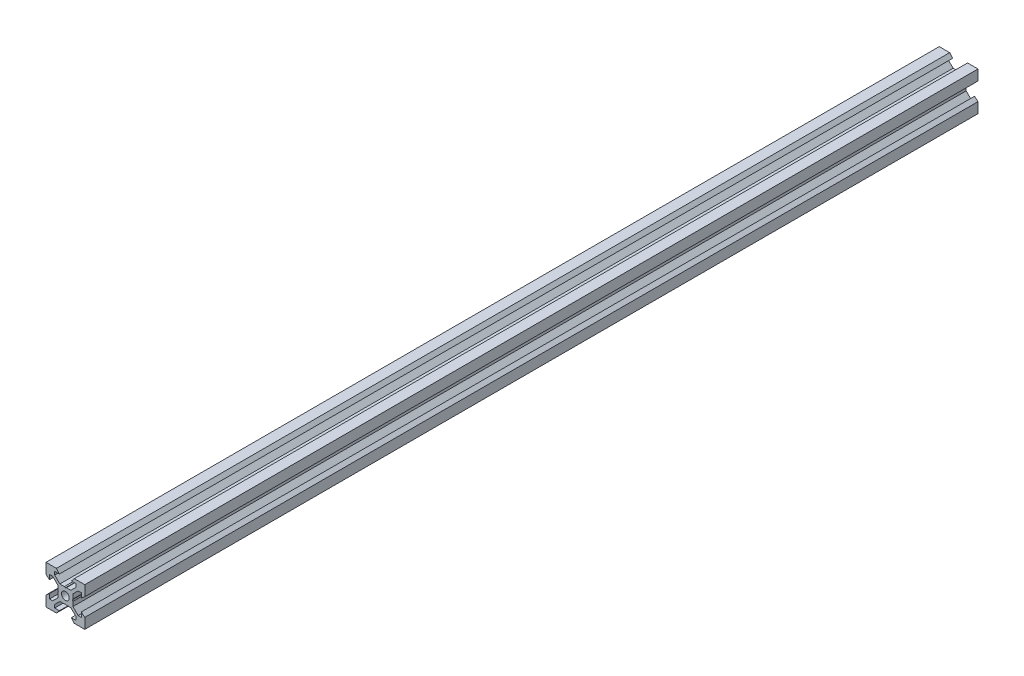
SolidWorks part; units mm, degrees
ref_plane "Front Plane" through (0, 0, 0) normal (0, 0, 1) x (1, 0, 0)
ref_plane "Top Plane" through (0, 0, 0) normal (0, 1, 0) x (1, 0, 0)
ref_plane "Right Plane" through (0, 0, 0) normal (1, 0, 0) x (0, 0, -1)
sketch "Sketch1" plane through (0, 0, 0) normal (0, 0, 1) x (1, 0, 0)
  line L0 (10, 10) -> (4.6104, 10) construction
  line L1 (10, 10) -> (10, 4.6104) construction
  line L2 (10, -10) -> (10, -4.6104) construction
  line L3 (10, -10) -> (4.6104, -10) construction
  line L4 (10, 10) -> (10, 4.6104)
  line L5 (6.5607, 5.5) -> (8.2, 5.5)
  line L6 (5.5, 8.2) -> (5.5, 6.5607)
  line L7 (10, 10) -> (4.6104, 10)
  line L8 (10, 10) -> (10, 4.6104)
  line L9 (6.5607, 5.5) -> (3.9, 2.8393)
  line L10 (5.5, 6.5607) -> (2.8393, 3.9)
  line L11 (10, 4.6104) -> (8.2, 3.1)
  line L12 (4.6104, 10) -> (3.1, 8.2)
  line L13 (8.2, 3.1) -> (8.2, 5.5)
  line L14 (3.1, 8.2) -> (5.5, 8.2)
  line L15 (-6.5607, 5.5) -> (-8.2, 5.5)
  line L16 (6.5607, -5.5) -> (8.2, -5.5)
  line L17 (3.1, -8.2) -> (5.5, -8.2)
  line L18 (8.2, -3.1) -> (8.2, -5.5)
  line L19 (4.6104, -10) -> (3.1, -8.2)
  line L20 (10, -4.6104) -> (8.2, -3.1)
  line L21 (0.5196, -3.9) -> (0, -3.6)
  line L22 (0.5196, 3.9) -> (0, 3.6)
  line L23 (3.6, 0) -> (3.9, -0.5196)
  line L24 (3.9, 0.5196) -> (3.6, 0)
  line L25 (3.9, 0.5196) -> (3.9, 2.8393)
  line L26 (2.8393, 3.9) -> (0.5196, 3.9)
  line L27 (3.9, -2.8393) -> (3.9, -0.5196)
  line L28 (2.8393, -3.9) -> (0.5196, -3.9)
  line L29 (5.5, -6.5607) -> (2.8393, -3.9)
  line L30 (6.5607, -5.5) -> (3.9, -2.8393)
  line L31 (10, -10) -> (10, -4.6104)
  line L32 (10, -10) -> (4.6104, -10)
  line L33 (5.5, -8.2) -> (5.5, -6.5607)
  line L34 (-6.5607, -5.5) -> (-8.2, -5.5)
  line L35 (10, -10) -> (10, -4.6104)
  line L36 (0, 0) -> (0, 8.2) construction
  line L37 (-10, -10) -> (-4.6104, -10) construction
  line L38 (-10, -10) -> (-10, -4.6104) construction
  line L39 (-10, 10) -> (-10, 4.6104) construction
  line L40 (-10, 10) -> (-4.6104, 10) construction
  line L41 (-10, -10) -> (-10, -4.6104)
  line L43 (-5.5, -8.2) -> (-5.5, -6.5607)
  line L44 (-10, -10) -> (-4.6104, -10)
  line L45 (-10, -10) -> (-10, -4.6104)
  line L46 (-6.5607, -5.5) -> (-3.9, -2.8393)
  line L47 (-5.5, -6.5607) -> (-2.8393, -3.9)
  line L48 (-2.8393, -3.9) -> (-0.5196, -3.9)
  line L49 (-3.9, -2.8393) -> (-3.9, -0.5196)
  line L50 (-2.8393, 3.9) -> (-0.5196, 3.9)
  line L51 (-3.9, 0.5196) -> (-3.9, 2.8393)
  line L52 (-3.9, 0.5196) -> (-3.6, 0)
  line L53 (-3.6, 0) -> (-3.9, -0.5196)
  line L54 (-0.5196, 3.9) -> (0, 3.6)
  line L55 (-0.5196, -3.9) -> (0, -3.6)
  line L56 (-10, -4.6104) -> (-8.2, -3.1)
  line L57 (-4.6104, -10) -> (-3.1, -8.2)
  line L58 (-8.2, -3.1) -> (-8.2, -5.5)
  line L59 (-3.1, -8.2) -> (-5.5, -8.2)
  line L60 (-10, -10) -> (10, -10) construction
  line L61 (-10, -10) -> (-10, 10) construction
  line L62 (-3.1, 8.2) -> (-5.5, 8.2)
  line L63 (-8.2, 3.1) -> (-8.2, 5.5)
  line L64 (-4.6104, 10) -> (-3.1, 8.2)
  line L65 (-10, 4.6104) -> (-8.2, 3.1)
  line L66 (-5.5, 6.5607) -> (-2.8393, 3.9)
  line L67 (-6.5607, 5.5) -> (-3.9, 2.8393)
  line L68 (-10, 10) -> (-10, 4.6104)
  line L69 (-10, 10) -> (-4.6104, 10)
  line L70 (-5.5, 8.2) -> (-5.5, 6.5607)
  line L71 (-10, 10) -> (10, 10) construction
  line L72 (-10, 10) -> (-10, 4.6104)
  line L73 (10, -10) -> (10, 10) construction
  line L74 (-10, -10) -> (10, 10) construction
  line L75 (-10, 10) -> (10, -10) construction
  circle A0 centre (0, 0) radius 2
  dimension "D7" = 4
  dimension "D1" = 20
  dimension "D2" = 5.3896
  dimension "D3" = 4.5
  dimension "D4" = 50
  dimension "D5" = 1.8
  dimension "D6" = 1.5104
  dimension "D8" = 5.5
  dimension "D9" = 120
  dimension "D10" = 0.3
  dimension "D11" = 2.3197
  dimension "D12" = 7.8
  dimension "D13" = 7.8
  dimension "D14" = 1.5
  dimension "D15" = 2.6607
extrude "Boss-Extrude1" add sketch "Sketch1" along normal mid plane 461 contours L70 L62 L64 L69 L68 L65 L63 L15 L67 L51 L52 L53 L49 L46 L34 L58 L56 L41 L44 L57 L59 L43 L47 L48 L55 L21 L28 L29 L33 L17 L19 L32 L31 L20 L18 L16 L30 L27 L23 L24 L25 L9 L5 L13 L11 L4 L7 L12 L14 L6 L10 region at (9.7172, 7.3052, 0)
